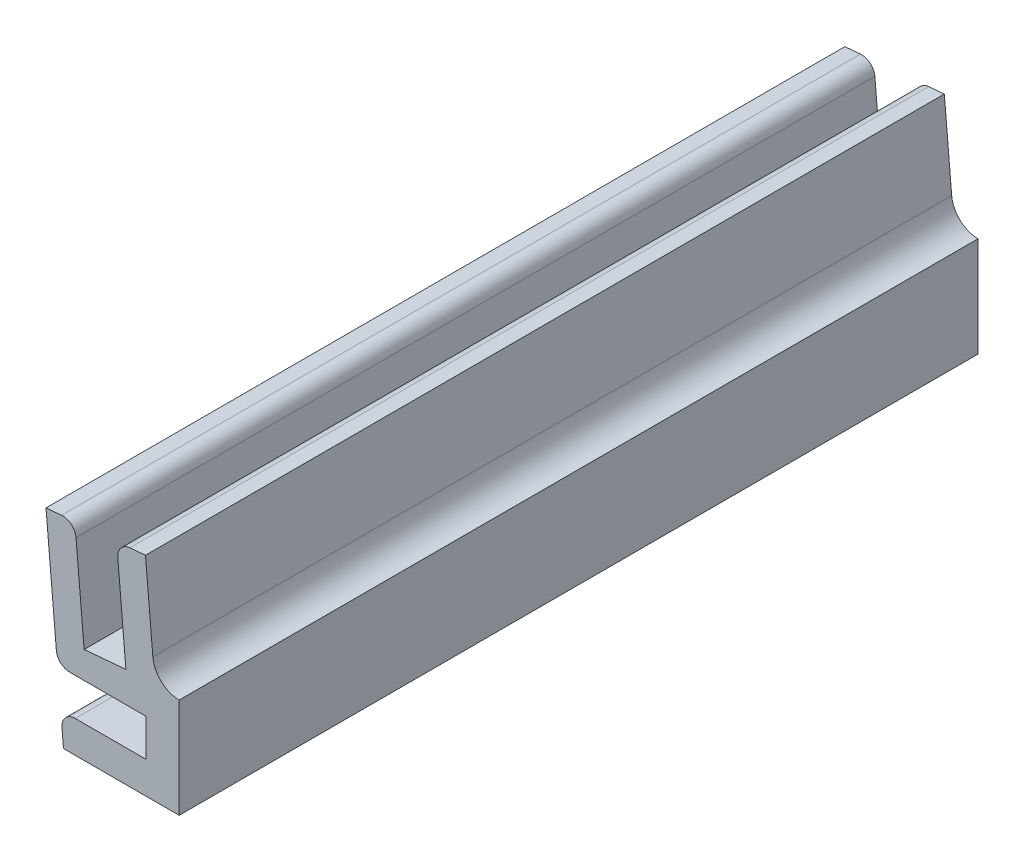
SolidWorks part; units mm, degrees
ref_plane "Front" through (0, 0, 0) normal (0, 0, 1) x (1, 0, 0)
ref_plane "Top" through (0, 0, 0) normal (0, 1, 0) x (1, 0, 0)
ref_plane "Right" through (0, 0, 0) normal (1, 0, 0) x (0, 0, -1)
sketch "Sketch1" plane through (0, 0, 0) normal (0, 0, 1) x (1, 0, 0)
  line L0 (0, 0) -> (-11.0333, 0)
  line L1 (-11.0333, 0) -> (-12.7, 19.05)
  line L2 (-12.7, 19.05) -> (-3.2112, 19.8802)
  line L3 (-3.2112, 19.8802) -> (-2.3053, 9.525)
  line L4 (-2.3053, 9.525) -> (0, 9.525)
  line L5 (0, 9.525) -> (0, 0)
  dimension "D1" = 12.7
  dimension "D2" = 19.05
  dimension "D3" = 9.525
  dimension "D4" = 9.525
  dimension "D5" = 95
extrude "Boss-Extrude1" add sketch "Sketch1" along normal mid plane 76.2
sketch "Sketch2" plane through (0, 0, 38.1) normal (0, 0, 1) x (1, 0, 0)
  line L0 (-5.9632, 19.6394) -> (-5.0777, 9.5181)
  line L1 (-3.2112, 19.8802) -> (-12.7, 19.05) construction
  line L2 (-5.0777, 9.5181) -> (-9.0625, 9.1694)
  line L3 (-9.0625, 9.1694) -> (-9.948, 19.2908)
  line L4 (-9.948, 19.2908) -> (-5.9632, 19.6394)
  line L5 (-11.6111, 6.604) -> (-3.175, 6.604)
  line L6 (-12.7, 19.05) -> (-11.0333, 0) construction
  line L7 (-3.175, 6.604) -> (-3.175, 3.048)
  line L8 (-3.175, 3.048) -> (-11.3, 3.048)
  line L9 (-11.3, 3.048) -> (-11.6111, 6.604)
  line L11 (-11.0333, 0) -> (0, 0) construction
  line L12 (0, 0) -> (0, 9.525) construction
  point P10 (-7.9556, 19.4651)
  point P13 (-7.9556, 19.4651)
  dimension "D1" = 4
  dimension "D3" = 10.16
  dimension "D4" = 3.556
  dimension "D5" = 3.048
  dimension "D6" = 3.175
extrude "Cut-Extrude1" cut sketch "Sketch2" against normal through all
fillet "Fillet1" radius 2.54 1 edges at (-2.3053, 9.525, 0)
fillet "Fillet2" radius 1.27 4 edges at (-11.3, 3.048, 0) (-11.6111, 6.604, 0) (-5.9632, 19.6394, 0) (-9.948, 19.2908, 0)
